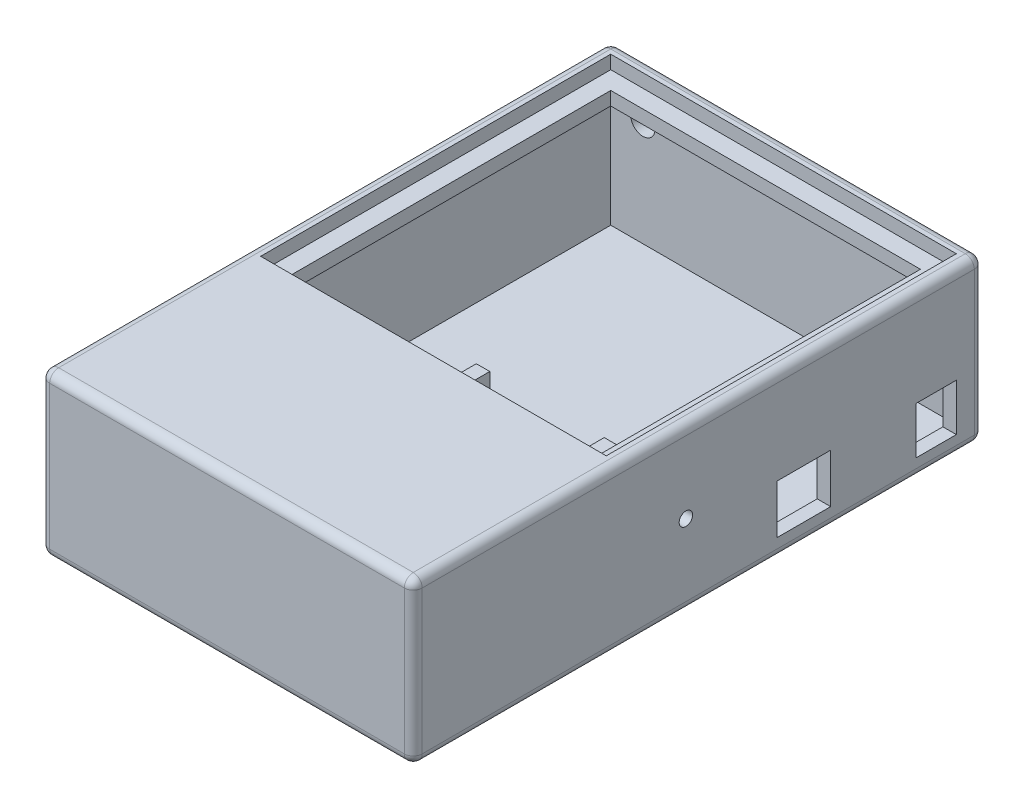
SolidWorks part; units mm, degrees
ref_plane "Front" through (0, 0, 0) normal (0, 0, 1) x (1, 0, 0)
ref_plane "Top" through (0, 0, 0) normal (0, 1, 0) x (1, 0, 0)
ref_plane "Right" through (0, 0, 0) normal (1, 0, 0) x (0, 0, -1)
sketch "Эскиз1" plane through (0, 0, 0) normal (0, 1, 0) x (1, 0, 0)
  line L1 (-83, 127) -> (0, 127)
  line L2 (-83, 127) -> (-83, 0)
  line L3 (-83, 0) -> (0, 0)
  line L4 (0, 127) -> (0, 0)
  dimension "D1" = 83
  dimension "D2" = 127
extrude "Бобышка-Вытянуть1" add sketch "Эскиз1" along normal blind 36
sketch "Эскиз2" plane through (0, 0, 0) normal (0, -1, 0) x (-1, 0, 0)
  line L0 (0, 0) -> (0, 127) construction
  line L1 (3, 43.7) -> (80, 43.7)
  line L2 (3, 43.7) -> (3, 3)
  line L3 (3, 3) -> (80, 3)
  line L4 (80, 43.7) -> (80, 3)
  line L5 (83, 0) -> (0, 0) construction
  dimension "D1" = 77
  dimension "D2" = 3
  dimension "D3" = 3
  dimension "D4" = 40.7
extrude "Вырез-Вытянуть1" cut sketch "Эскиз2" against normal blind 22.9
sketch "Эскиз3" plane through (0, 36, 0) normal (0, 1, 0) x (1, 0, 0)
  line L0 (-83, 0) -> (0, 0) construction
  line L1 (-80, 124) -> (-3, 124)
  line L2 (-80, 124) -> (-80, 46)
  line L3 (-80, 46) -> (-3, 46)
  line L4 (-3, 124) -> (-3, 46)
  line L5 (-83, 127) -> (-83, 0) construction
  line L6 (0, 0) -> (0, 127) construction
  line L7 (0, 127) -> (-83, 127) construction
  dimension "D1" = 46
  dimension "D2" = 3
  dimension "D3" = 3
  dimension "D4" = 3
extrude "Вырез-Вытянуть4" cut sketch "Эскиз3" against normal blind 33
sketch "Эскиз4" plane through (0, 3, 0) normal (0, 1, 0) x (1, 0, 0)
  line L0 (-80, 46) -> (-3, 46) construction
  line L1 (-57.25, 71.3) -> (-25.75, 71.3)
  line L2 (-57.25, 71.3) -> (-57.25, 46)
  line L3 (-57.25, 46) -> (-25.75, 46)
  line L4 (-25.75, 71.3) -> (-25.75, 46)
  line L5 (-80, 124) -> (-80, 46) construction
  dimension "D1" = 31.5
  dimension "D2" = 25.3
  dimension "D3" = 22.75
extrude "Бобышка-Вытянуть2" add sketch "Эскиз4" along normal blind 11
sketch "Эскиз5" plane through (0, 14, 0) normal (0, 1, 0) x (1, 0, 0)
  line L0 (-57.25, 71.3) -> (-57.25, 46) construction
  line L1 (-54.25, 71.3) -> (-28.75, 71.3)
  line L2 (-54.25, 71.3) -> (-54.25, 48)
  line L3 (-54.25, 48) -> (-28.75, 48)
  line L4 (-28.75, 71.3) -> (-28.75, 48)
  line L5 (-57.25, 46) -> (-25.75, 46) construction
  line L6 (-25.75, 71.3) -> (-57.25, 71.3) construction
  dimension "D1" = 3
  dimension "D2" = 25.5
  dimension "D3" = 2
  dimension "D4" = 0
extrude "Вырез-Вытянуть5" cut sketch "Эскиз5" against normal blind 11
sketch "Эскиз6" plane through (0, 0, 0) normal (1, 0, 0) x (0, 0, -1)
  line L0 (0, 36) -> (127, 36) construction
  circle A0 centre (60.7429, 18) radius 1.5
  point P4 (0, 0)
  dimension "D1" = 18
extrude "Вырез-Вытянуть6" cut sketch "Эскиз6" against normal blind 10 and the other way blind 14
sketch "Эскиз7" plane through (0, 0, -43.7) normal (0, 0, 1) x (1, 0, 0)
  line L0 (-3, 22.9) -> (-3, 0) construction
  line L1 (-80, 22.9) -> (-3, 22.9) construction
  circle A0 centre (-5.5, 19.4) radius 2.5
  dimension "D1" = 2.5
  dimension "D2" = 3.5
extrude "Вырез-Вытянуть7" cut sketch "Эскиз7" against normal blind 22
sketch "Эскиз8" plane through (0, 0, -127) normal (0, 0, -1) x (-1, 0, 0)
  circle A0 centre (72.842, 26.4254) radius 2.7
extrude "Вырез-Вытянуть8" cut sketch "Эскиз8" against normal blind 30 and the other way blind 23
sketch "Эскиз9" plane through (-3, 0, 0) normal (-1, 0, 0) x (0, 0, 1)
  line L0 (-46, 3) -> (-46, 19.4) construction
  line L1 (-93, 15.1) -> (-81, 15.1)
  line L2 (-93, 15.1) -> (-93, 4.2)
  line L3 (-93, 4.2) -> (-81, 4.2)
  line L4 (-81, 15.1) -> (-81, 4.2)
  line L5 (-46, 3) -> (-124, 3) construction
  dimension "D1" = 35
  dimension "D2" = 10.9
  dimension "D3" = 12
  dimension "D4" = 1.2
extrude "Вырез-Вытянуть9" cut sketch "Эскиз9" against normal blind 33 and the other way blind 11
sketch "Эскиз10" plane through (-3, 0, 0) normal (-1, 0, 0) x (0, 0, 1)
  line L0 (-93, 15.1) -> (-93, 4.2) construction
  line L1 (-121, 14.6) -> (-112, 14.6)
  line L2 (-121, 14.6) -> (-121, 4.1)
  line L3 (-121, 4.1) -> (-112, 4.1)
  line L4 (-112, 14.6) -> (-112, 4.1)
  line L5 (-46, 3) -> (-124, 3) construction
  dimension "D1" = 19
  dimension "D2" = 10.5
  dimension "D3" = 1.1
  dimension "D4" = 9
extrude "Вырез-Вытянуть10" cut sketch "Эскиз10" against normal blind 36 and the other way blind 14
sketch "Эскиз11" plane through (-3, 0, 0) normal (-1, 0, 0) x (0, 0, 1)
  line L0 (-124, 3) -> (-124, 36) construction
  line L1 (-124, 33) -> (-46, 33)
  line L2 (-124, 33) -> (-124, 30)
  line L3 (-124, 30) -> (-46, 30)
  line L4 (-46, 33) -> (-46, 30)
  line L5 (-46, 36) -> (-124, 36) construction
  dimension "D1" = 78
  dimension "D2" = 0
  dimension "D3" = 3
  dimension "D4" = 3
extrude "Бобышка-Вытянуть3" add sketch "Эскиз11" along normal blind 4
sketch "Эскиз12" plane through (0, 0, -124) normal (0, 0, 1) x (1, 0, 0)
  line L0 (-3, 36) -> (-80, 36) construction
  line L1 (-76, 33) -> (-7, 33)
  line L2 (-76, 33) -> (-76, 30)
  line L3 (-76, 30) -> (-7, 30)
  line L4 (-7, 33) -> (-7, 30)
  line L5 (-7, 33) -> (-7, 30) construction
  dimension "D1" = 3
  dimension "D2" = 3
  dimension "D3" = 69
  dimension "D4" = 0
extrude "Бобышка-Вытянуть4" add sketch "Эскиз12" along normal blind 4
sketch "Эскиз13" plane through (-80, 0, 0) normal (1, 0, 0) x (0, 0, -1)
  line L0 (124, 3) -> (124, 36) construction
  line L1 (46, 33) -> (124, 33)
  line L2 (46, 33) -> (46, 30)
  line L3 (46, 30) -> (124, 30)
  line L4 (124, 33) -> (124, 30)
  line L5 (124, 36) -> (46, 36) construction
  dimension "D1" = 78
  dimension "D2" = 0
  dimension "D3" = 3
  dimension "D4" = 3
extrude "Бобышка-Вытянуть5" add sketch "Эскиз13" along normal blind 4
ref_plane "Плоскость5" through (-76, 30, -46) normal (0, -1, 0) x (-1, 0, 0)
sketch "Эскиз15" plane through (0, 0, -46) normal (0, 0, -1) x (-1, 0, 0)
  line L0 (80, 36) -> (3, 36) construction
  line L1 (7, 33) -> (76, 33)
  line L2 (7, 33) -> (7, 30)
  line L3 (7, 30) -> (76, 30)
  line L4 (76, 33) -> (76, 30)
  line L5 (7, 30) -> (7, 33) construction
  dimension "D1" = 3
  dimension "D2" = 3
  dimension "D3" = 69
  dimension "D4" = 0
extrude "Бобышка-Вытянуть6" add sketch "Эскиз15" along normal blind 2
sketch "Эскиз16" plane through (0, 0, 0) normal (0, -1, 0) x (-1, 0, 0)
  line L1 (3, 3) -> (1.5, 3)
  line L2 (3, 3) -> (3, 44.5)
  line L3 (3, 44.5) -> (1.5, 44.5)
  line L4 (1.5, 3) -> (1.5, 44.5)
  point P9 (2.25, 44.5)
  dimension "D1" = 1.5
  dimension "D2" = 41.5
extrude "Вырез-Вытянуть11" cut sketch "Эскиз16" against normal blind 2
sketch "Эскиз17" plane through (0, 0, 0) normal (0, -1, 0) x (1, 0, 0)
  line L1 (-1.5, -45.2) -> (-80, -45.2)
  line L2 (-1.5, -45.2) -> (-1.5, -43.7)
  line L3 (-1.5, -43.7) -> (-80, -43.7)
  line L4 (-80, -45.2) -> (-80, -43.7)
  dimension "D1" = 78.5
  dimension "D2" = 1.5
extrude "Вырез-Вытянуть12" cut sketch "Эскиз17" against normal blind 2
sketch "Эскиз19" plane through (0, 0, 0) normal (0, -1, 0) x (1, 0, 0)
  line L1 (-80, -45.2) -> (-81.5, -45.2)
  line L2 (-80, -45.2) -> (-80, -2.9889)
  line L3 (-80, -2.9889) -> (-81.5, -2.9889)
  line L4 (-81.5, -45.2) -> (-81.5, -2.9889)
  dimension "D1" = 1.5
extrude "Вырез-Вытянуть13" cut sketch "Эскиз19" against normal blind 2
fillet "Скругление1" radius 2 1 edges at (-41.5, 36, -127)
fillet "Скругление2" radius 2 3 edges at (-83, 17, -127) (-83, 35.4142, -126.4142) (-83, 36, -62.5)
fillet "Скругление3" radius 2 3 edges at (-83, 17, 0) (-82.4142, 35.4142, 0) (-40.5, 36, 0)
fillet "Скругление4" radius 2 5 edges at (0, 17, 0) (0, 35.4142, -0.5858) (0, 17, -127) (0, 35.4142, -126.4142) (0, 36, -63.5)
fillet "Скругление5" radius 2 8 edges at (-0.5858, 0, -126.4142) (0, 0, -63.5) (-0.5858, 0, -0.5858) (-41.5, 0, 0) (-82.4142, 0, -0.5858) (-83, 0, -63.5) (-82.4142, 0, -126.4142) (-41.5, 0, -127)
sketch "Эскиз20" plane through (0, 0, 0) normal (0, -1, 0) x (1, 0, 0)
  line L0 (-81, -45.2) -> (-2, -45.2) construction
  line L1 (-11, -55.2) -> (-19, -55.2)
  line L2 (-11, -55.2) -> (-11, -45.2)
  line L3 (-11, -45.2) -> (-19, -45.2)
  line L4 (-19, -55.2) -> (-19, -45.2)
  line L5 (-2, -125) -> (-2, -45.2) construction
  dimension "D1" = 10
  dimension "D2" = 8
  dimension "D3" = 9
extrude "Вырез-Вытянуть14" cut sketch "Эскиз20" against normal blind 2
sketch "Эскиз21" plane through (0, 0, 0) normal (0, -1, 0) x (1, 0, 0)
  line L0 (-81, -45.2) -> (-19, -45.2) construction
  line L1 (-64, -55.2) -> (-72, -55.2)
  line L2 (-64, -55.2) -> (-64, -45.2)
  line L3 (-64, -45.2) -> (-72, -45.2)
  line L4 (-72, -55.2) -> (-72, -45.2)
  line L5 (-81, -45.2) -> (-81, -125) construction
  dimension "D1" = 9
  dimension "D2" = 10
  dimension "D3" = 8
extrude "Вырез-Вытянуть15" cut sketch "Эскиз21" against normal blind 2
sketch "Эскиз22" plane through (0, 2, 0) normal (0, -1, 0) x (1, 0, 0)
  line L0 (-19, -55.2) -> (-11, -55.2) construction
  line L1 (-19, -45.2) -> (-19, -55.2) construction
  circle A0 centre (-15, -51.2) radius 1.5
  dimension "D1" = 4
  dimension "D2" = 4
extrude "Вырез-Вытянуть16" cut sketch "Эскиз22" along normal blind 102 and the other way blind 85
sketch "Эскиз23" plane through (0, 2, 0) normal (0, -1, 0) x (1, 0, 0)
  line L0 (-72, -55.2) -> (-64, -55.2) construction
  line L1 (-72, -45.2) -> (-72, -55.2) construction
  circle A0 centre (-68, -51.2) radius 1.5
  dimension "D1" = 4
  dimension "D2" = 4
extrude "Вырез-Вытянуть17" cut sketch "Эскиз23" against normal blind 68 and the other way blind 37
